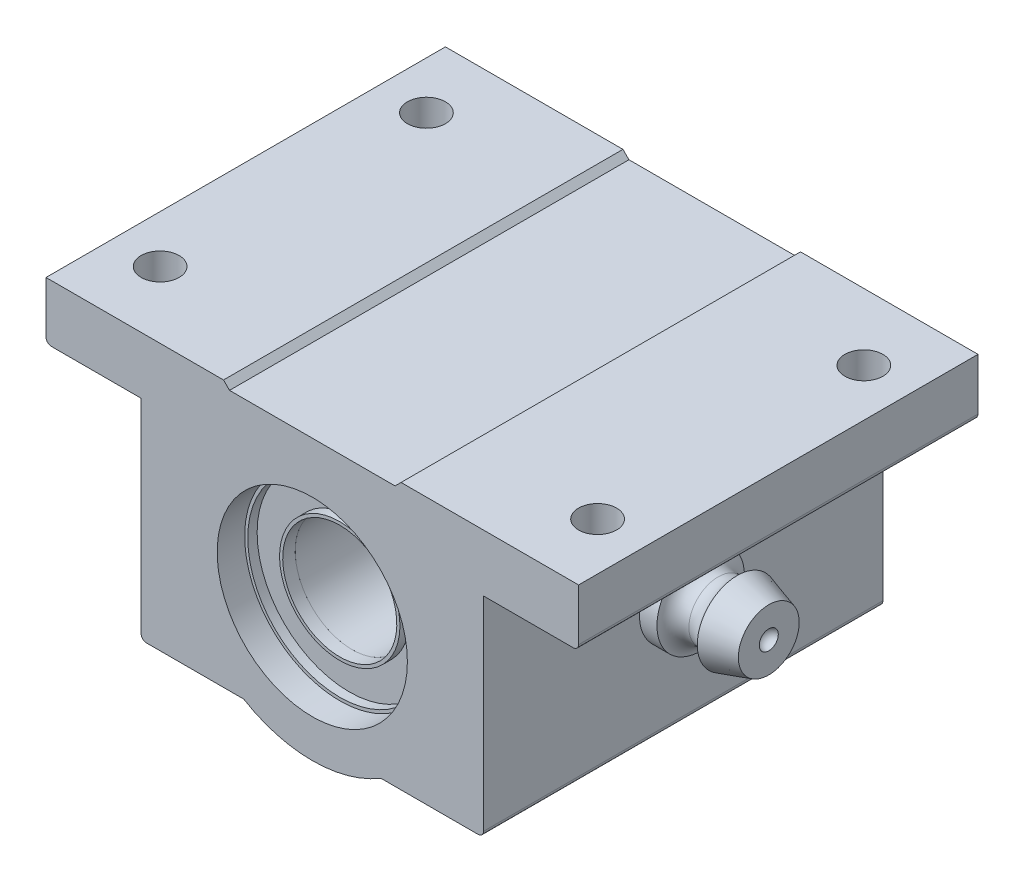
SolidWorks part; units mm, degrees
other "Pillow Block"
other "Linear Bearing"
other "Seal  "
ref_plane "Front" through (0, 0, 0) normal (0, 0, 1) x (1, 0, 0)
ref_plane "Top" through (0, 0, 0) normal (0, 1, 0) x (1, 0, 0)
ref_plane "Right" through (0, 0, 0) normal (1, 0, 0) x (0, 0, -1)
sketch "Sketch1" plane through (0, 0, 0) normal (0, 0, 1) x (1, 0, 0)
  line L0 (-14.2875, -11.1125) -> (-14.2875, 7.9375) construction
  line L1 (-14.2875, -11.1125) -> (14.2875, -11.1125) construction
  line L2 (-14.2875, 7.9375) -> (-22.225, 7.9375)
  line L3 (-22.225, 12.7) -> (22.225, 12.7) construction
  line L4 (-22.225, 7.9375) -> (-22.225, 12.7)
  line L5 (14.2875, -11.1125) -> (14.2875, 7.9375) construction
  line L6 (14.2875, 7.9375) -> (22.225, 7.9375)
  line L7 (22.225, 7.9375) -> (22.225, 12.7)
  line L8 (0, 12.7) -> (0, -11.1125) construction
  line L9 (5.7238, -9.525) -> (14.2875, -9.525)
  line L10 (-14.2875, 7.9375) -> (-14.2875, -9.525)
  line L11 (-14.2875, -9.525) -> (-5.7238, -9.525)
  line L12 (14.2875, -9.525) -> (14.2875, 7.9375)
  line L13 (-7.4083, 12.7) -> (7.4083, 12.7) construction
  line L14 (-7.4083, 12.7) -> (-6.907, 12.1987)
  line L15 (-6.907, 12.1987) -> (6.907, 12.1987)
  line L16 (6.907, 12.1987) -> (7.4083, 12.7)
  line L17 (-7.4083, 12.7) -> (-22.225, 12.7)
  line L18 (7.4083, 12.7) -> (22.225, 12.7)
  circle A0 centre (0, 0) radius 4.7625 construction
  circle A1 centre (0, 0) radius 7.9375
  circle A2 centre (0, 0) radius 11.1125 construction
  arc A3 (-5.7238, -9.525) -> (5.7238, -9.525) centre (0, 0) ccw
  dimension "D1" = 0.5013
  dimension "For Shaft Dia" = 9.525
  dimension "Ht G" = 12.7
  dimension "Flange Thick H" = 4.7625
  dimension "Overall Wd D" = 44.45
  dimension "Overall Ht F" = 23.8125
  dimension "Supplier Wd G" = 28.575
  dimension "D3" = 45
  dimension "D4" = 45
  dimension "D6" = 14.8167
  dimension "Supplier Body Height K" = 22.225
extrude "Main Body" add sketch "Sketch1" along normal mid plane 33.3375
sketch "Sketch8" plane through (0, 0, 0) normal (0, 0, 1) x (1, 0, 0)
  circle A0 centre (0, 0) radius 7.9375 construction
  circle A1 centre (0, 0) radius 7.9375
  circle A2 centre (0, 0) radius 4.7625 construction
  circle A3 centre (0, 0) radius 4.7625
extrude "Interior" add sketch "Sketch8" along normal offset from surface 3.3337 and the other way offset from surface 3.3337 separate body up to face at (0, 4.8043, 16.6687) other way up to face at (0, 4.8043, -16.6687)
fillet "Fillets" radius 0.4465 4 edges at (14.2875, -9.525, 0) (-14.2875, -9.525, 0) (-22.225, 7.9375, 0) (22.225, 7.9375, 0)
sketch "Sketch3" plane through (0, 12.7, 0) normal (0, 1, 0) x (1, 0, 0)
  line L0 (-5.7238, 0) -> (5.7238, 0) construction
  line L1 (-18.2563, -11.1125) -> (18.2563, -11.1125) construction
  line L2 (-18.2563, -11.1125) -> (-18.2563, 11.1125) construction
  line L3 (-18.2563, 11.1125) -> (18.2563, 11.1125) construction
  line L4 (18.2563, -11.1125) -> (18.2563, 11.1125) construction
  line L5 (-18.2563, -11.1125) -> (18.2563, 11.1125) construction
  line L6 (-18.2563, 11.1125) -> (18.2563, -11.1125) construction
  circle A0 centre (-18.2563, 11.1125) radius 1.5875
  circle A1 centre (18.2563, 11.1125) radius 1.5875
  circle A2 centre (18.2563, -11.1125) radius 1.5875
  circle A3 centre (-18.2563, -11.1125) radius 1.5875
  point P0 (0, 0)
  dimension "Dia L" = 3.175
  dimension "Mounting Holes Center-to-Center J" = 36.5125
  dimension "Mounting Holes Center-to-Center K" = 22.225
extrude "Mounting Holes" cut sketch "Sketch3" against normal up to surface (4.7625 mm away) up to face at (18.033, 7.9375, 0)
sketch "Seal" plane through (0, 0, 0) normal (1, 0, 0) x (0, 0, -1)
  line L0 (-13.335, 4.7625) -> (-14.3768, 4.7625)
  line L1 (-13.335, 4.7625) -> (-13.335, -4.7625) construction
  line L2 (-14.3768, 4.7625) -> (-14.3768, 5.0229)
  line L3 (-14.3768, 5.0229) -> (-13.5954, 5.0229)
  line L4 (-13.5954, 5.0229) -> (-13.5954, 7.6771)
  line L5 (-13.5954, 7.6771) -> (-14.3768, 7.6771)
  line L6 (-14.3768, 7.6771) -> (-14.3768, 7.9375)
  line L7 (-16.6687, 7.9375) -> (16.6687, 7.9375) construction
  line L8 (-14.3768, 7.9375) -> (-13.335, 7.9375)
  line L9 (-13.335, 7.9375) -> (-13.335, 4.7625)
  line L10 (0, 0) -> (-16.6687, 0) construction
  line L11 (-16.6687, -9.0785) -> (-16.6687, 7.9375) construction
  dimension "D1" = 0.2604
  dimension "D3" = 0.2604
  dimension "D4" = 1.0418
revolve "Seal " add sketch "Seal" angle 360 mid plane about L10
sketch "Grease Fitting" plane through (0, 0, 0) normal (0, 0, 1) x (1, 0, 0)
  line L0 (14.2875, 0) -> (21.4313, 0) construction
  line L1 (14.2875, -9.525) -> (14.2875, 7.9375) construction
  line L2 (14.2875, 0) -> (14.2875, 3.6512)
  line L3 (14.2875, 3.6512) -> (15.748, 3.6512)
  line L4 (17.2085, 0) -> (17.2085, 2.4447) construction
  line L5 (17.2085, 2.4447) -> (18.796, 2.4447) construction
  line L6 (18.796, 0) -> (18.796, 3.3337) construction
  line L7 (21.4313, 0) -> (21.4313, 2.54) construction
  line L8 (18.796, 3.3337) -> (21.4313, 2.54)
  line L9 (15.748, 3.6512) -> (15.748, 0) construction
  line L10 (21.4313, 2.54) -> (21.4313, 0.7937)
  line L11 (20.6375, 0) -> (14.2875, 0)
  line L12 (14.2875, -9.0785) -> (14.2875, 7.9375) construction
  line L13 (0, 0) -> (14.2875, 0) construction
  arc A0 (17.2085, 2.4447) -> (15.748, 3.6512) centre (17.2085, 3.932) cw
  circle A1 centre (21.4313, 0) radius 0.7937 construction
  arc A2 (17.2085, 2.4447) -> (18.796, 3.3337) centre (17.2085, 4.3067) ccw
  arc A3 (21.4313, 0.7937) -> (20.6375, 0) centre (21.4313, 0) ccw
  dimension "D9" = 1.5875
  dimension "D1" = 1.4605
  dimension "D2" = 3.6512
  dimension "D3" = 2.4447
  dimension "D4" = 3.3337
  dimension "D5" = 2.54
  dimension "D6" = 7.1437
  dimension "D7" = 1.4605
  dimension "D8" = 1.5875
revolve "Grease Fitting " add sketch "Grease Fitting" angle 360 mid plane about L11
sketch "Slot Opening" [suppressed] plane through (0, 0, 0) normal (0, 0, 1) x (1, 0, 0)
  line L0 (0, 0) -> (0, -21.997) construction
  line L1 (-12.7, -21.997) -> (12.7, -21.997)
  line L2 (-12.7, -21.997) -> (-21.997, -38.1)
  line L3 (12.7, -21.997) -> (21.997, -38.1)
  line L4 (21.997, -38.1) -> (31.149, -38.1)
  line L5 (-31.149, -38.1) -> (-21.997, -38.1)
  line L6 (31.149, -38.1) -> (31.149, -49.2125)
  line L7 (31.149, -49.2125) -> (-31.149, -49.2125)
  line L8 (-31.149, -49.2125) -> (-31.149, -38.1)
  line L9 (-57.15, -49.2125) -> (57.15, -49.2125) construction
  circle A0 centre (0, 0) radius 25.4 construction
  dimension "D1" = 60
  dimension "Wd E" = 25.4
extrude "Slot Opening " [suppressed] cut sketch "Slot Opening" against normal up to surface and the other way blind 33.3375
mirror "Seal Mirror" about plane through (0, 0, 0) normal (0, 0, 1) of bodies 125 127
equation "\"D6@Sketch1\" = \"Overall Wd D@Sketch1\" / 3"
equation "\"D1@Fillets\" = \"Supplier Wd G@Sketch1\" / 64"
equation "\"D1@Sketch1\" = \"Flange Thick H@Sketch1\" / 9.5"
equation "\"D1@Interior\" = \"Overall Lg B@Main Body\" * .1"
equation "\"D2@Interior\" = \"D1@Interior\""
equation "\"D2@Slot Opening \" = \"Overall Lg B@Main Body\""
equation "\"D4@Seal\" = \"D1@Interior\" * .3125"
equation "\"D3@Seal\" = \"D4@Seal\" * .25"
equation "\"D1@Seal\" = \"D3@Seal\""
